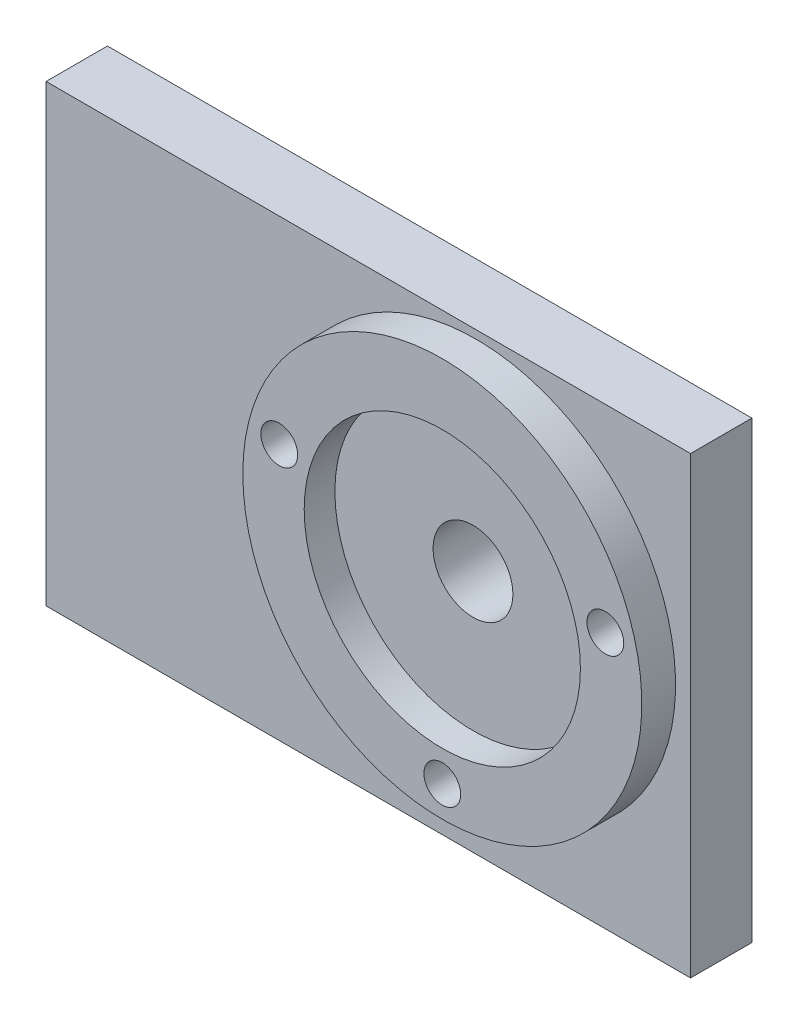
SolidWorks part; units mm, degrees
note: '?' marks a value the reader was unsure of.
ref_plane "Plan de face" through (0, 0, 0) normal (0, 0, 1) x (1, 0, 0)
ref_plane "Plan de dessus" through (0, 0, 0) normal (0, 1, 0) x (1, 0, 0)
ref_plane "Plan de droite" through (0, 0, 0) normal (1, 0, 0) x (0, 0, -1)
sketch "Esquisse1" plane through (0, 0, 0) normal (0, 0, 1) x (1, 0, 0)
  circle A0 centre (0, 0) radius 32.5
  dimension "D1" = 65
extrude "Boss.-Extru.1" add sketch "Esquisse1" along normal blind 5
sketch "Esquisse2" plane through (0, 0, 5) normal (0, 0, 1) x (1, 0, 0)
  circle A0 centre (0, 0) radius 22.5
  dimension "D1" = 45
extrude "Enlèv. mat.-Extru.1" cut sketch "Esquisse2" against normal blind 2.5
sketch "Esquisse3" plane through (0, 0, 2.5) normal (0, 0, 1) x (1, 0, 0)
  circle A0 centre (0, 0) radius 6.5
  dimension "D1" = 13
extrude "Enlèv. mat.-Extru.2" cut sketch "Esquisse3" against normal through all
hole_wizard "Trous de centrage Ø6.0mm1" positions "Esquisse5" profile "Esquisse4" hole size "Ø6.0" standard "ISO" end condition through all
sketch "Esquisse5" plane through (0, 0, 5) normal (0, 0, 1) x (1, 0, 0)
  point P0 (0, -27.5)
  point P2 (-26.563, 7.1175)
  point P4 (26.563, 7.1175)
sketch "Esquisse4" plane through (0, -27.5, 5) normal (1, 0, 0) x (0, -1, 0)
  line L0 (0, 0) -> (0, 5)
  line L1 (0, 5) -> (3, 5)
  line L2 (3, 5) -> (3, 0)
  line L5 (3, 0) -> (0, 0)
  line L11 (0, -6.35) -> (0, 107.95) construction
  dimension "Diamètre du perçage jusqu'au prochain" = 6
  dimension "Profondeur du perçage jusqu'au prochain" = 5
ref_axis "Axe1" through (0, 0, 5) along (0, 0, -1)?
sketch "Esquisse6" plane through (0, 0, 0) normal (0, 0, -1) x (-1, 0, 0)
  line L1 (70.0552, 33.8323) -> (-34.9448, 33.8323)
  line L2 (70.0552, 33.8323) -> (70.0552, -40.1677)
  line L3 (70.0552, -40.1677) -> (-34.9448, -40.1677)
  line L4 (-34.9448, 33.8323) -> (-34.9448, -40.1677)
  line L5 (70.0552, 33.8323) -> (-34.9448, -40.1677) construction
  line L6 (70.0552, -40.1677) -> (-34.9448, 33.8323) construction
  point P0 (0, 0)
  circle M10 centre (0, 0) radius 32.5
  dimension "D1" = 74
  dimension "D2" = 105
extrude "Boss.-Extru.2" add sketch "Esquisse6" against normal blind 10 contours L1 L4 L3 L2 M10
sketch "Esquisse7" plane through (0, 0, 5) normal (0, 0, 1) x (1, 0, 0)
  line L0 (-34.4957, -40.1677) -> (-34.4957, 33.8323)
  line L1 (-34.4957, -40.1677) -> (34.2911, -40.1677)
  line L2 (-34.4957, 33.8323) -> (34.2911, 33.8323)
  line L3 (34.2911, -40.1677) -> (34.2911, 33.8323)
  line L4 (-70.0552, -40.1677) -> (34.9448, -40.1677) construction
  line L5 (-70.0552, 33.8323) -> (34.9448, 33.8323) construction
extrude "Boss.-Extru.3" add sketch "Esquisse7" along normal blind 10.5
hole_wizard "Chambrage pour vis à tête ronde bombée M61" positions "Esquisse15" profile "Esquisse14" counterbore size "M6" standard "Ansi Metric"
sketch "Esquisse15" plane through (0, 0, 0) normal (0, 0, -1) x (-1, 0, 0)
  point P0 (0, -27.5)
  point P2 (26.563, 7.1175)
  point P4 (-26.563, 7.1175)
sketch "Esquisse14" plane through (0, -27.5, 0) normal (1, 0, 0) x (0, 1, 0)
  line L0 (0, 0) -> (0, 6.9828)
  line L1 (0, 6.9828) -> (3.3, 5)
  line L2 (3.3, 5) -> (3.3, 4.625)
  line L3 (3.3, 4.625) -> (3.325, 4.6)
  line L4 (3.325, 4.6) -> (6.5, 4.6)
  line L5 (6.5, 4.6) -> (6.5, 0)
  line L6 (6.5, 0) -> (0, 0)
  line L9 (-3.3, 4.625) -> (-3.325, 4.6) construction
  line L10 (0, 6.9828) -> (-3.3, 5) construction
  line L11 (0, -6.35) -> (0, 107.95) construction
  dimension "Diamètre du perçage" = 6.6
  dimension "Profondeur du perçage" = 5
  dimension "Diamètre du chambrage" = 13
  dimension "Profondeur du chambrage" = 4.6
  dimension "Diamètre du fraisage milieu" = 6.65
  dimension "Angle du fraisage milieu" = 90
  dimension "Angle de pointe" = 118
sketch "Esquisse16" plane through (0, 0, 2.5) normal (0, 0, 1) x (1, 0, 0)
  circle A0 centre (0, 0) radius 22.5
  arc M1 (-3.7437, -22.1864) -> (3.7437, -22.1864) centre (0, -27.5) cw
  arc M2 (3.7437, -22.1864) -> (22.3993, 2.1261) centre (0, 0) ccw
  arc M3 (22.3993, 2.1261) -> (20.4614, 9.3584) centre (26.563, 7.1175) cw
  arc M4 (20.4614, 9.3584) -> (-20.4614, 9.3584) centre (0, 0) ccw
  arc M5 (-20.4614, 9.3584) -> (-22.3993, 2.1261) centre (-26.563, 7.1175) cw
  arc M6 (-22.3993, 2.1261) -> (-3.7437, -22.1864) centre (0, 0) ccw
  circle M7 centre (0, 0) radius 6.5
extrude "Boss.-Extru.4" add sketch "Esquisse16" along normal blind 8 contours M6 M1 M2 M3 M4 M5 M7 | A0 M3 | A0 M1 | A0 M5
hole_wizard "Chambrage pour vis à tête ronde bombée M62" positions "Esquisse18" profile "Esquisse17" counterbore size "M6" standard "Ansi Metric"
sketch "Esquisse18" plane through (0, 0, 0) normal (0, 0, -1) x (-1, 0, 0)
  point P0 (26.563, 7.1175)
sketch "Esquisse17" plane through (-26.563, 7.1175, 0) normal (1, 0, 0) x (0, 1, 0)
  line L0 (0, 0) -> (0, 6.9828)
  line L1 (0, 6.9828) -> (3.3, 5)
  line L2 (3.3, 5) -> (3.3, 4.625)
  line L3 (3.3, 4.625) -> (3.325, 4.6)
  line L4 (3.325, 4.6) -> (6.5, 4.6)
  line L5 (6.5, 4.6) -> (6.5, 0)
  line L6 (6.5, 0) -> (0, 0)
  line L9 (-3.3, 4.625) -> (-3.325, 4.6) construction
  line L10 (0, 6.9828) -> (-3.3, 5) construction
  line L11 (0, -6.35) -> (0, 107.95) construction
  dimension "Diamètre du perçage" = 6.6
  dimension "Profondeur du perçage" = 5
  dimension "Diamètre du chambrage" = 13
  dimension "Profondeur du chambrage" = 4.6
  dimension "Diamètre du fraisage milieu" = 6.65
  dimension "Angle du fraisage milieu" = 90
  dimension "Angle de pointe" = 118
hole_wizard "Chambrage pour vis à tête ronde bombée M63" positions "Esquisse20" profile "Esquisse19" counterbore size "M6" standard "Ansi Metric"
sketch "Esquisse20" plane through (0, 0, 0) normal (0, 0, -1) x (-1, 0, 0)
  point P0 (0, -27.5)
  point P2 (-26.563, 7.1175)
sketch "Esquisse19" plane through (0, -27.5, 0) normal (1, 0, 0) x (0, 1, 0)
  line L0 (0, 0) -> (0, 6.9828)
  line L1 (0, 6.9828) -> (3.3, 5)
  line L2 (3.3, 5) -> (3.3, 4.625)
  line L3 (3.3, 4.625) -> (3.325, 4.6)
  line L4 (3.325, 4.6) -> (6.5, 4.6)
  line L5 (6.5, 4.6) -> (6.5, 0)
  line L6 (6.5, 0) -> (0, 0)
  line L9 (-3.3, 4.625) -> (-3.325, 4.6) construction
  line L10 (0, 6.9828) -> (-3.3, 5) construction
  line L11 (0, -6.35) -> (0, 107.95) construction
  dimension "Diamètre du perçage" = 6.6
  dimension "Profondeur du perçage" = 5
  dimension "Diamètre du chambrage" = 13
  dimension "Profondeur du chambrage" = 4.6
  dimension "Diamètre du fraisage milieu" = 6.65
  dimension "Angle du fraisage milieu" = 90
  dimension "Angle de pointe" = 118
hole_wizard "Dégagement M33" positions "Esquisse22" profile "Esquisse21" hole size "M3" standard "JIS"
sketch "Esquisse22" plane through (0, 0, 0) normal (0, 0, -1) x (-1, 0, 0)
  point P0 (55.5475, -22.2941)
  point P2 (36.229, -17.1177)
  point P4 (55.5475, 22.2941)
  point P6 (36.229, 17.1177)
  point P8 (38.2649, 10.8722)
  point P10 (30.6999, 25.0583)
  point P12 (37.2389, 26.8104)
  point P14 (38.2649, -10.8722)
  point P16 (37.2389, -26.8104)
  point P18 (30.6999, -25.0583)
  point P20 (62.2938, 3.775)
  point P22 (62.2938, -3.775)
sketch "Esquisse21" plane through (-55.5475, -22.2941, 0) normal (1, 0, 0) x (0, 1, 0)
  line L0 (0, 0) -> (0, 5.9815)
  line L1 (0, 5.9815) -> (1.7, 5)
  line L2 (1.7, 5) -> (1.7, 0)
  line L5 (1.7, 0) -> (0, 0)
  line L10 (0, 5.9815) -> (-1.7, 5) construction
  line L11 (0, -6.35) -> (0, 107.95) construction
  dimension "Diamètre du perçage" = 3.4
  dimension "Profondeur du perçage" = 5
  dimension "Angle de pointe" = 120
hole_wizard "Dégagement M42" positions "Esquisse25" profile "Esquisse23" hole size "M4" standard "JIS"
sketch "Esquisse25" plane through (0, 0, 0) normal (0, 0, -1) x (-1, 0, 0)
  point P0 (38.2938, 0)
sketch "Esquisse23" plane through (-38.2938, 0, 0) normal (1, 0, 0) x (0, 1, 0)
  line L0 (0, 0) -> (0, 6.299)
  line L1 (0, 6.299) -> (2.25, 5)
  line L2 (2.25, 5) -> (2.25, 0)
  line L5 (2.25, 0) -> (0, 0)
  line L10 (0, 6.299) -> (-2.25, 5) construction
  line L11 (0, -6.35) -> (0, 107.95) construction
  dimension "Diamètre du perçage" = 4.5
  dimension "Profondeur du perçage" = 5
  dimension "Angle de pointe" = 120
hole_wizard "Dégagement M43" positions "Esquisse27" profile "Esquisse26" hole size "M4" standard "JIS"
sketch "Esquisse27" plane through (0, 0, 0) normal (0, 0, -1) x (-1, 0, 0)
  point P0 (62.4201, 28.9061)
sketch "Esquisse26" plane through (-62.4201, 28.9061, 0) normal (1, 0, 0) x (0, 1, 0)
  line L0 (0, 0) -> (0, 6.299)
  line L1 (0, 6.299) -> (2.25, 5)
  line L2 (2.25, 5) -> (2.25, 0)
  line L5 (2.25, 0) -> (0, 0)
  line L10 (0, 6.299) -> (-2.25, 5) construction
  line L11 (0, -6.35) -> (0, 107.95) construction
  dimension "Diamètre du perçage" = 4.5
  dimension "Profondeur du perçage" = 5
  dimension "Angle de pointe" = 120
hole_wizard "Dégagement M44" positions "Esquisse29" profile "Esquisse28" hole size "M4" standard "JIS"
sketch "Esquisse29" plane through (0, 0, 0) normal (0, 0, -1) x (-1, 0, 0)
  point P0 (61.9305, -28.2644)
sketch "Esquisse28" plane through (-61.9305, -28.2644, 0) normal (1, 0, 0) x (0, 1, 0)
  line L0 (0, 0) -> (0, 6.299)
  line L1 (0, 6.299) -> (2.25, 5)
  line L2 (2.25, 5) -> (2.25, 0)
  line L5 (2.25, 0) -> (0, 0)
  line L10 (0, 6.299) -> (-2.25, 5) construction
  line L11 (0, -6.35) -> (0, 107.95) construction
  dimension "Diamètre du perçage" = 4.5
  dimension "Profondeur du perçage" = 5
  dimension "Angle de pointe" = 120
hole_wizard "Dégagement M45" positions "Esquisse31" profile "Esquisse30" hole size "M4" standard "JIS"
sketch "Esquisse31" plane through (0, 0, 0) normal (0, 0, -1) x (-1, 0, 0)
  point P0 (23.6285, -35.9128)
  point P2 (23.6285, 29.5773)
  point P4 (-29.3715, 29.5773)
  point P6 (-29.3715, -35.9128)
sketch "Esquisse30" plane through (-23.6285, -35.9128, 0) normal (1, 0, 0) x (0, 1, 0)
  line L0 (0, 0) -> (0, 4.299)
  line L1 (0, 4.299) -> (2.25, 3)
  line L2 (2.25, 3) -> (2.25, 0)
  line L5 (2.25, 0) -> (0, 0)
  line L10 (0, 4.299) -> (-2.25, 3) construction
  line L11 (0, -6.35) -> (0, 107.95) construction
  dimension "Diamètre du perçage" = 4.5
  dimension "Profondeur du perçage" = 3
  dimension "Angle de pointe" = 120
